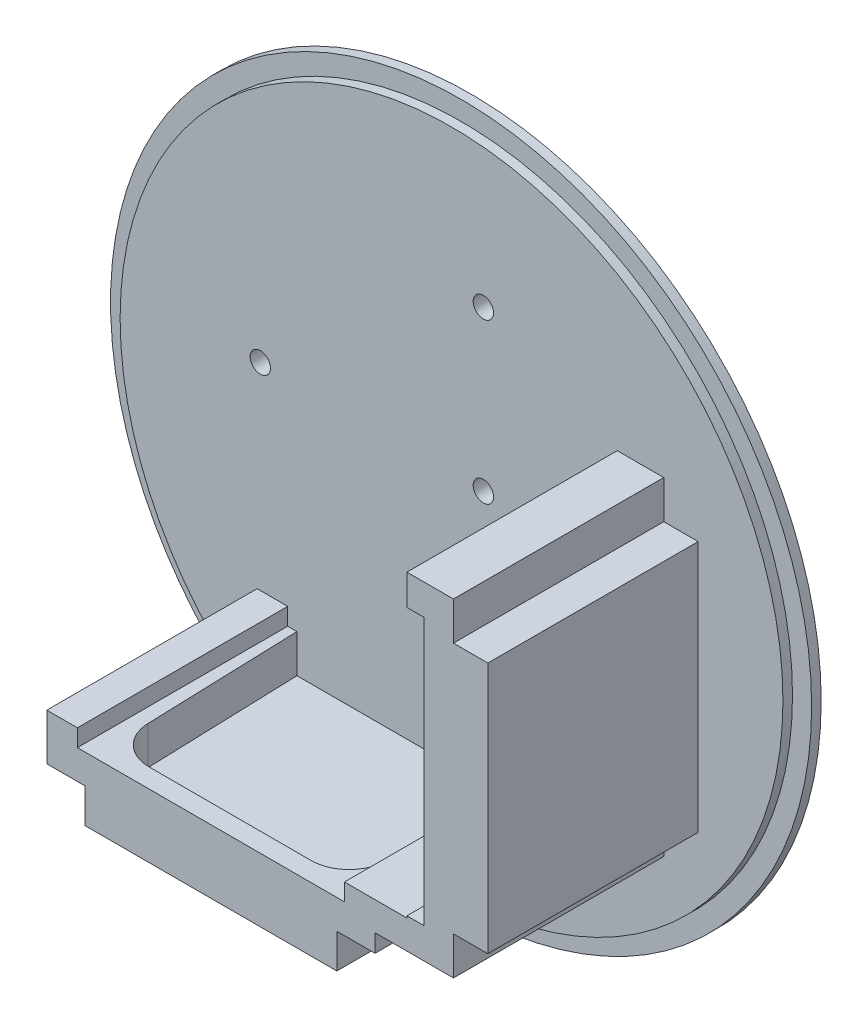
SolidWorks part; units mm, degrees
material "ABS"
ref_plane "Ebene vorne" through (0, 0, 0) normal (0, 0, 1) x (1, 0, 0)
ref_plane "Ebene oben" through (0, 0, 0) normal (0, 1, 0) x (1, 0, 0)
ref_plane "Ebene rechts" through (0, 0, 0) normal (1, 0, 0) x (0, 0, -1)
sketch "Skizze1" plane through (0, 0, 0) normal (0, 0, 1) x (1, 0, 0)
  circle A0 centre (0, 0) radius 55
  circle A1 centre (0, 0) radius 52
  point P15 (0, 0)
  point P23 (0, 0)
  dimension "D1" = 110
  dimension "D2" = 3
extrude "Aufsatz-Linear austragen1" add sketch "Skizze1" along normal blind 3 contours A1 region at (0, 0, 0)
extrude "Aufsatz-Linear austragen2" add sketch "Skizze1<3>" along normal blind 1.5 contours A0 A1 region at (-53.4444, 0, 0)
sketch "Skizze1<3>" plane through (0, 0, 0) normal (0, 0, 1) x (1, 0, 0) same geometry as "Skizze1"
sketch "Skizze2" plane through (0, 0, 3) normal (0, 0, 1) x (1, 0, 0)
  line L0 (25.9967, -4.75) -> (33.2967, -4.75) construction
  line L1 (26, 21) -> (26, 16.2)
  line L2 (26, 16.2) -> (27.2, 16.2)
  line L3 (26, 21) -> (33.3, 21)
  line L4 (33.3, -30.5) -> (33.3, -24.5)
  line L5 (27.2, -25.7) -> (26, -25.7)
  line L6 (27.2, 16.2) -> (28.7, 16.2)
  line L7 (28.7, 16.2) -> (28.7, 15)
  line L8 (38.7, 15) -> (33.3, 15)
  line L9 (38.7, -24.5) -> (33.3, -24.5)
  line L10 (28.7, -25.7) -> (28.7, -24.5)
  line L11 (27.2, -25.7) -> (28.7, -25.7)
  line L12 (26, -25.7) -> (26, -26)
  line L13 (33.3, 21) -> (33.3, 15)
  line L14 (26, -30.5) -> (33.3, -30.5)
  line L15 (16.2, -27.2) -> (16.2, -26)
  line L16 (16.2, -26) -> (21, -26)
  line L17 (-25.7, -27.2) -> (-25.7, -26)
  line L18 (-25.7, -26) -> (-30.5, -26)
  line L19 (21, -30.5) -> (21, -33.3)
  line L20 (-30.5, -33.3) -> (-24.5, -33.3)
  line L21 (15, -38.7) -> (15, -33.3)
  line L22 (16.2, -27.2) -> (16.2, -28.7)
  line L23 (16.2, -28.7) -> (15, -28.7)
  line L24 (-24.5, -38.7) -> (-24.5, -33.3)
  line L26 (-25.7, -28.7) -> (-24.5, -28.7)
  line L27 (-25.7, -27.2) -> (-25.7, -28.7)
  line L28 (15, -28.7) -> (-24.5, -28.7)
  line L29 (21, -33.3) -> (15, -33.3)
  line L30 (-30.5, -26) -> (-30.5, -33.3)
  line L32 (15, -38.7) -> (-24.5, -38.7)
  line L33 (-4.75, -25.9967) -> (-4.75, -33.2967) construction
  line L34 (26, -30.5) -> (21, -30.5)
  line L35 (21, -26) -> (26, -26)
  line L38 (28.7, -24.5) -> (28.7, 15)
  line L40 (38.7, -24.5) -> (38.7, 15)
  line L41 (21, -26) -> (21, -33.3) [skipped]
  point P1 (0, 0)
  point P41 (0, 0)
  dimension "D2" = 5.4
  dimension "D6" = 2
  dimension "D7" = 6
  dimension "D8" = 19.75
  dimension "D10" = 10
sketch "Skizze3" plane through (0, 0, 3) normal (0, 0, 1) x (1, 0, 0)
  circle A0 centre (4.995, 4.9959) radius 1.6
  circle A1 centre (4.995, 29.9959) radius 1.6
  circle A2 centre (-30.005, 4.9959) radius 1.6
  dimension "D1" = 3.2
  dimension "D2" = 3.2
  dimension "D3" = 3.2
extrude "Schnitt-Linear austragen1" cut sketch "Skizze3" against normal up to next
extrude "Aufsatz-Linear austragen3" add sketch "Skizze2" along normal blind 33 contours L38 L7 L6 L2 L1 L3 L13 L8 L40 L9 L4 L14 L34 L19 L29 L21 L32 L24 L20 L30 L18 L17 L27 L26 L28 L23 L22 L15 L16 L35 L12 L5 L11 L10
sketch "Skizze6" plane through (0, -38.7, 0) normal (0, -1, 0) x (1, 0, 0)
  line L0 (-4.75, 36) -> (-4.75, 3) construction
  line L1 (15, 36) -> (-24.5, 36) construction
  line L2 (15, 3) -> (-24.5, 3) construction
  line L3 (-24.25, 3) -> (-23.25, 33)
  line L4 (-23.25, 33) -> (13.75, 33)
  line L5 (-24.25, 3) -> (14.75, 3)
  line L6 (14.75, 3) -> (13.75, 33)
  point P11 (-4.75, 33)
  point P12 (-4.75, 33)
  dimension "D1" = 19.5
  dimension "D2" = 18.5
  dimension "D3" = 30
extrude "Schnitt-Linear austragen4" cut sketch "Skizze6" against normal up to next from offset 4 contours L3 L4 L6 L5 offset against normal yes
fillet "Verrundung1" radius 6 2 edges at (-23.25, -31.7, 33) (13.75, -31.7, 33)
sketch "Skizze7" plane through (28.7, 0, 0) normal (-1, 0, 0) x (0, 0, 1)
  line L0 (36, -4.75) -> (3, -4.75) construction
  line L1 (36, -25.7) -> (36, 16.2) construction
  line L2 (3, 16.2) -> (3, -25.7) construction
  line L3 (33, -23.25) -> (33, 13.75)
  line L4 (3, -24.25) -> (3, 14.75)
  line L5 (33, 13.75) -> (3, 14.75)
  line L6 (33, -23.25) -> (3, -24.25)
  point P11 (33, -4.75)
  dimension "D1" = 18.5
  dimension "D2" = 19.5
  dimension "D3" = 30
extrude "Schnitt-Linear austragen9" cut sketch "Skizze7" against normal blind 6 contours L3 L5 L4 L6
fillet "Verrundung2" radius 6 2 edges at (31.7, -23.25, 33) (31.7, 13.75, 33)
